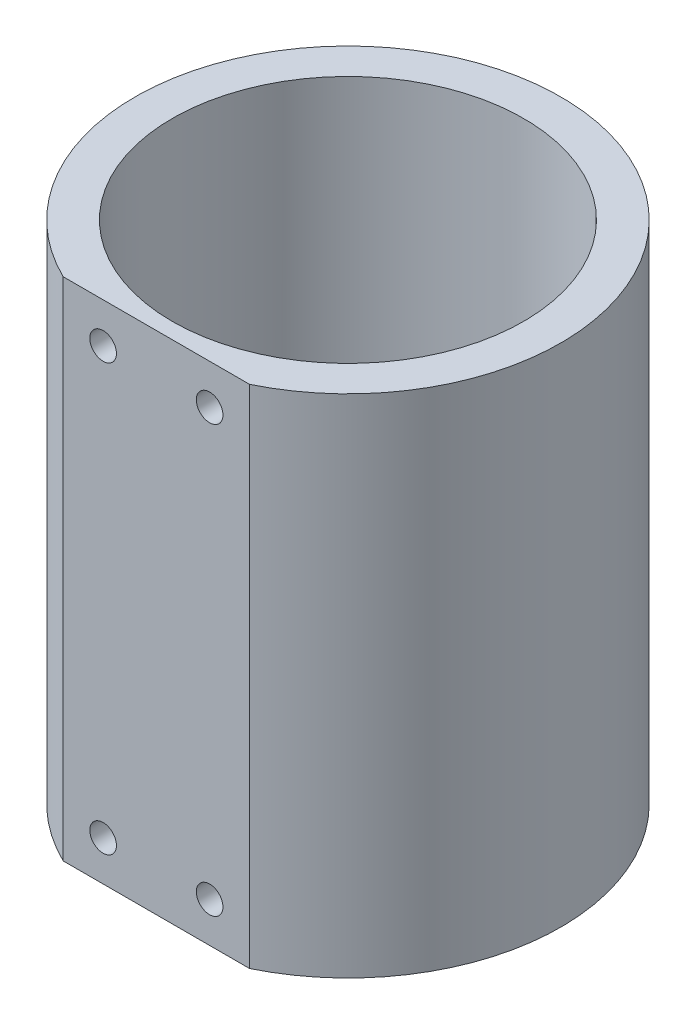
SolidWorks part; units mm, degrees
ref_plane "Front Plane" through (0, 0, 0) normal (0, 0, 1) x (1, 0, 0)
ref_plane "Top Plane" through (0, 0, 0) normal (0, 1, 0) x (1, 0, 0)
ref_plane "Right Plane" through (0, 0, 0) normal (1, 0, 0) x (0, 0, -1)
sketch "Sketch1" plane through (0, 0, 0) normal (0, 1, 0) x (1, 0, 0)
  line L0 (-17.5, -35.9687) -> (17.5, -35.9687)
  arc A1 (17.5, -35.9687) -> (-17.5, -35.9687) centre (0, 0) ccw
  point P2 (0, 0)
  point P4 (0, 0)
  point P5 (0, 0)
  point P6 (0, 0)
  point P7 (0, -33)
  dimension "D1" = 80
  dimension "D2" = 35
extrude "Boss-Extrude1" add sketch "Sketch1" along normal mid plane 15
sketch "Sketch2" plane through (0, 7.5, 0) normal (0, 1, 0) x (1, 0, 0)
  circle A0 centre (0, 0) radius 2.625
  dimension "D1" = 5.25
extrude "Cut-Extrude1" cut sketch "Sketch2" against normal through all
sketch "Sketch3" plane through (0, 7.5, 0) normal (0, 1, 0) x (1, 0, 0)
  line L0 (-544.3881, -544.3881) -> (26675.0155, 26675.0155) construction
  line L1 (0, -1000) -> (0, 49000) construction
  circle A0 centre (14.8492, 14.8492) radius 2.125
  dimension "D1" = 4.25
  dimension "D2" = 21
  dimension "D3" = 45
extrude "Cut-Extrude2" cut sketch "Sketch3" against normal through all
pattern_circular "CirPattern1" count 4 over 360 about axis through (0, 7.5, 0) along (0, 1, 0) of "Cut-Extrude2"
sketch "Sketch4" plane through (0, 7.5, 0) normal (0, 1, 0) x (1, 0, 0)
  line L0 (0, 15) -> (8.146, 15)
  line L1 (8.146, 15) -> (19.6545, 26.5085)
  line L4 (0, 33) -> (0, -48146.9727) construction
  line L5 (0, 33) -> (0, 15)
  arc A0 (19.6545, 26.5085) -> (0, 33) centre (0, 0) ccw
  dimension "D2" = 66
  dimension "D1" = 15
  dimension "D3" = 135
  dimension "D6" = 8.146
extrude "Cut-Extrude3" cut sketch "Sketch4" against normal through all
mirror "Mirror1" about plane through (0, -7.5, -33) normal (-1, 0, 0) of "Cut-Extrude3"
sketch "Sketch7" plane through (0, 7.5, 0) normal (0, 1, 0) x (1, 0, 0)
  circle A0 centre (0, 0) radius 5
  dimension "D1" = 10
extrude "Cut-Extrude6" cut sketch "Sketch7" against normal blind 5
chamfer "Chamfer1" distance 4 angle 45 1 edges at (0, 2.5, 5)
sketch "Sketch8" plane through (0, 7.5, 0) normal (0, -1, 0) x (1, 0, 0)
  line L0 (-17.5, 35.9687) -> (17.5, 35.9687)
  arc A0 (-17.5, 35.9687) -> (17.5, 35.9687) centre (0, 0) ccw
  circle A1 centre (0, 0) radius 33
  dimension "D1" = 66
extrude "Boss-Extrude2" add sketch "Sketch8" against normal offset from surface (80 mm away) 95 up to face at (0, -7.5, -22.3771)
sketch "Sketch9" plane through (0, 0, 35.9687) normal (0, 0, 1) x (1, 0, 0)
  line L10 (0, -1000) -> (0, 49000) construction
  line L11 (-17.5, -7.5) -> (17.5, -7.5) construction
  line L12 (-10, 0) -> (10, 0) construction
  line L13 (-10, 0) -> (-10, 80) construction
  line L14 (-10, 80) -> (10, 80) construction
  line L15 (10, 0) -> (10, 80) construction
  line L16 (-10, 0) -> (10, 80) construction
  line L17 (-10, 80) -> (10, 0) construction
  circle A1 centre (-10, 80) radius 2.5
  circle A2 centre (10, 80) radius 2.5
  circle A3 centre (10, 0) radius 2.5
  circle A4 centre (-10, 0) radius 2.5
  point P1 (0, 40)
  dimension "D4" = 5
  dimension "D5" = 5
  dimension "D6" = 5
  dimension "D7" = 5
  dimension "D1" = 80
  dimension "D2" = 20
  dimension "D3" = 7.5
extrude "Cut-Extrude7" cut sketch "Sketch9" against normal blind 5
